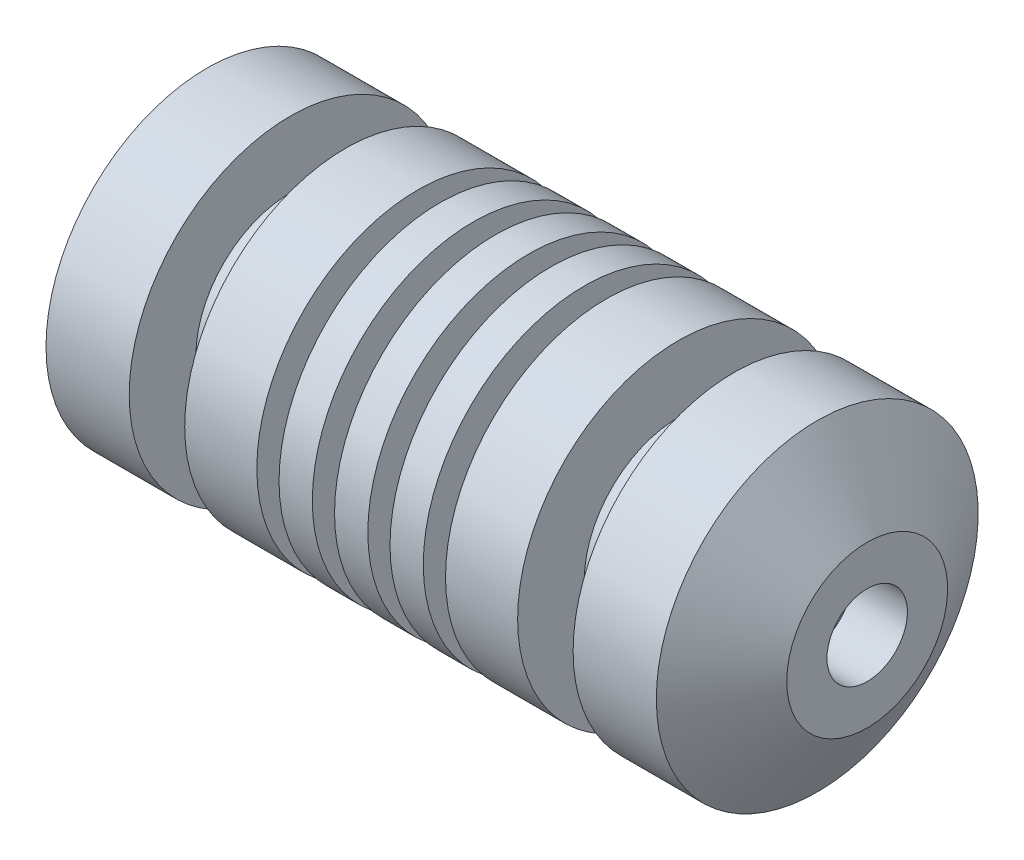
SolidWorks part; units mm, degrees
ref_plane "Front Plane" through (0, 0, 0) normal (0, 0, 1) x (1, 0, 0)
ref_plane "Top Plane" through (0, 0, 0) normal (0, 1, 0) x (1, 0, 0)
ref_plane "Right Plane" through (0, 0, 0) normal (1, 0, 0) x (0, 0, -1)
sketch "Sketch1" plane through (0, 0, 0) normal (0, 0, 1) x (1, 0, 0)
  line L0 (0, 0) -> (113.03, 0)
  line L42 (0, 36.83) -> (19.05, 36.83)
  line L43 (48.26, 36.83) -> (48.26, 29.21)
  line L44 (60.96, 36.83) -> (60.96, 29.21)
  line L45 (19.05, 36.83) -> (19.05, 21.59)
  line L46 (73.66, 36.83) -> (73.66, 29.21)
  line L48 (86.36, 36.83) -> (86.36, 29.21)
  line L49 (107.95, 36.83) -> (107.95, 21.59)
  line L50 (31.75, 36.83) -> (31.75, 21.59)
  line L52 (53.34, 36.83) -> (53.34, 29.21)
  line L53 (139.7, 36.83) -> (151.13, 18.415)
  line L54 (120.65, 36.83) -> (120.65, 21.59)
  line L55 (19.05, 21.59) -> (31.75, 21.59)
  line L56 (66.04, 36.83) -> (66.04, 29.21)
  line L57 (78.74, 36.83) -> (78.74, 29.21)
  line L58 (91.44, 36.83) -> (91.44, 29.21)
  line L59 (48.26, 29.21) -> (53.34, 29.21)
  line L60 (107.95, 21.59) -> (120.65, 21.59)
  line L61 (53.34, 36.83) -> (60.96, 36.83)
  line L62 (60.96, 29.21) -> (66.04, 29.21)
  line L63 (66.04, 36.83) -> (73.66, 36.83)
  line L64 (73.66, 29.21) -> (78.74, 29.21)
  line L65 (78.74, 36.83) -> (86.36, 36.83)
  line L66 (86.36, 29.21) -> (91.44, 29.21)
  line L67 (91.44, 36.83) -> (107.95, 36.83)
  line L68 (31.75, 36.83) -> (48.26, 36.83)
  line L69 (120.65, 36.83) -> (139.7, 36.83)
  line L70 (0, 36.83) -> (0, 0)
  line L74 (151.13, 18.415) -> (151.13, 9.2075)
  line L75 (151.13, 9.2075) -> (138.43, 9.2075)
  line L76 (138.43, 9.2075) -> (138.43, 6.35)
  line L77 (138.43, 6.35) -> (125.73, 6.35)
  line L78 (125.73, 6.35) -> (125.73, 3.81)
  line L79 (125.73, 3.81) -> (113.03, 3.81)
  line L80 (113.03, 3.81) -> (113.03, 0)
  dimension "D4" = 36.83
revolve "Revolve5" add sketch "Sketch1" angle 360 about L0
